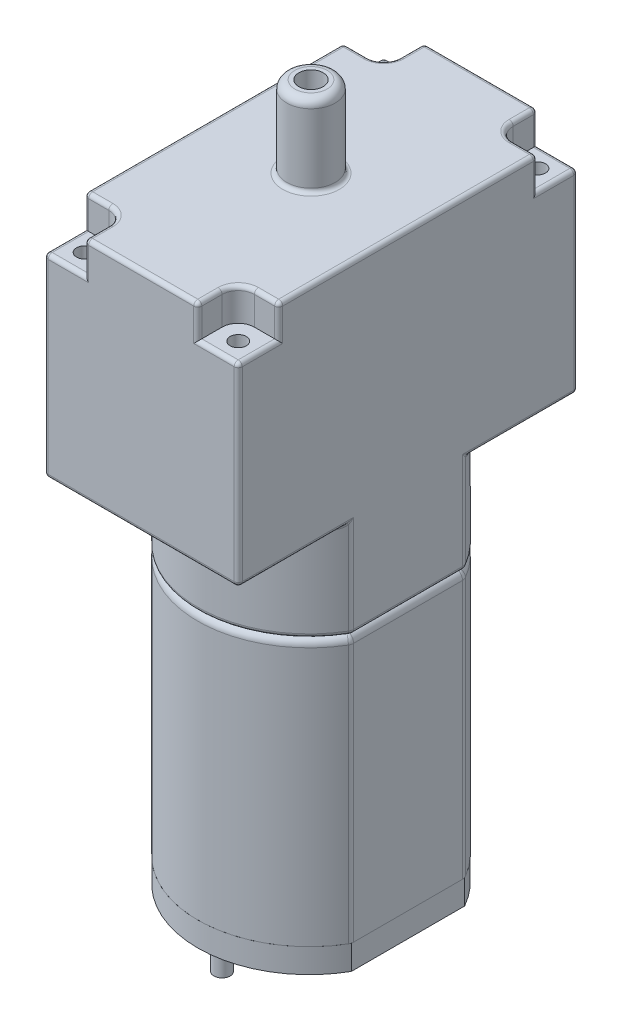
SolidWorks part; units mm, degrees
note: The reader was unsure of these and kept them because the rebuilt part matched: shared geometry of "Sketch4<3>".
ref_plane "Front Plane" through (0, 0, 0) normal (0, 0, 1) x (1, 0, 0)
ref_plane "Top Plane" through (0, 0, 0) normal (0, 1, 0) x (1, 0, 0)
ref_plane "Right Plane" through (0, 0, 0) normal (1, 0, 0) x (0, 0, -1)
sketch "Sketch1" plane through (0, 0, 0) normal (0, 1, 0) x (1, 0, 0)
  line L0 (-6, 3.5) -> (-6, -3.5)
  line L3 (-16.5353, 7) -> (21.0822, 7) construction
  line L4 (-19.3341, -7) -> (20.6889, -7) construction
  line L5 (6, 3.5) -> (6, -3.5)
  arc A1 (-6, 3.5) -> (6, 3.5) centre (0, 0.1071) cw
  arc A2 (-6, -3.5) -> (6, -3.5) centre (0, -0.1071) ccw
  point P3 (6, 0)
  dimension "D2" = 14
  dimension "D1" = 12
  dimension "D3" = 6
  dimension "D4" = 7
  dimension "D5" = 7
extrude "Boss-Extrude1" add sketch "Sketch1" along normal blind 1.5 contours A1 L5 A2 L0
sketch "Sketch3" plane through (0, 0, 0) normal (0, -1, 0) x (1, 0, 0)
  circle A0 centre (0, 0) radius 3
  dimension "D1" = 6
extrude "Boss-Extrude3" add sketch "Sketch3" along normal blind 1
sketch "Sketch4" plane through (0, 0, 0) normal (0, -1, 0) x (1, 0, 0)
  circle A0 centre (0, -5.5) radius 0.5
  circle A1 centre (0, 5.5) radius 0.5
  dimension "D3" = 1
  dimension "D1" = 11
  dimension "D2" = 5.5
extrude "Boss-Extrude5" add sketch "Sketch4" along normal blind 2 contours A1
extrude "Boss-Extrude6" add sketch "Sketch4<3>" along normal blind 2 contours A0
sketch "Sketch4<3>" plane through (0, 0, 0) normal (0, -1, 0) x (1, 0, 0) same geometry as "Sketch4"
sketch "Sketch2" plane through (0, 1.5, 0) normal (0, 1, 0) x (1, 0, 0)
  line L2 (-6, 3.5) -> (-6, -3.5)
  line L3 (6, -3.5) -> (6, 3.5)
  line L4 (-6, 3.5) -> (-6, -3.5)
  line L5 (6, -3.5) -> (6, 3.5)
  arc A2 (-6, -3.5) -> (6, -3.5) centre (0, -0.1071) ccw
  arc A3 (6, 3.5) -> (-6, 3.5) centre (0, 0.1071) ccw
  arc A4 (-6, -3.5) -> (6, -3.5) centre (0, -0.1071) ccw
  arc A5 (6, 3.5) -> (-6, 3.5) centre (0, 0.1071) ccw
  dimension "D1" = 0
extrude "Boss-Extrude2" add sketch "Sketch2" along normal blind 16.5 separate body
sketch "Sketch5" plane through (0, 18, 0) normal (0, 1, 0) x (1, 0, 0)
  line L2 (-6, 3.5) -> (-6, -3.5)
  line L3 (6, -3.5) -> (6, 3.5)
  line L4 (-6, 3.5) -> (-6, -3.5)
  line L5 (6, -3.5) -> (6, 3.5)
  arc A2 (6, 3.5) -> (-6, 3.5) centre (0, 0.1071) ccw
  arc A3 (-6, -3.5) -> (6, -3.5) centre (0, -0.1071) ccw
  arc A4 (6, 3.5) -> (-6, 3.5) centre (0, 0.1071) ccw
  arc A5 (-6, -3.5) -> (6, -3.5) centre (0, -0.1071) ccw
  dimension "D1" = 0
extrude "Boss-Extrude7" add sketch "Sketch5" along normal blind 6 separate body
sketch "Sketch6" plane through (0, 24, 0) normal (0, 1, 0) x (1, 0, 0)
  line L0 (6, -3.5) -> (6, 3.5) construction
  line L1 (-6, 10.5) -> (6, 10.5)
  line L2 (-6, 10.5) -> (-6, -10.5)
  line L3 (-6, -10.5) -> (6, -10.5)
  line L4 (6, 10.5) -> (6, -10.5)
  line L5 (-6, 10.5) -> (6, -10.5) construction
  line L6 (-6, -10.5) -> (6, 10.5) construction
  point P0 (0, 0)
  dimension "D1" = 21
extrude "Boss-Extrude8" add sketch "Sketch6" along normal blind 14
sketch "Sketch7" plane through (0, 38, 0) normal (0, 1, 0) x (1, 0, 0)
  circle A0 centre (0, 0) radius 1.5
  circle A1 centre (0, 0) radius 0.75
  dimension "D1" = 3
  dimension "D2" = 1.5
extrude "Boss-Extrude9" add sketch "Sketch7" along normal blind 5
sketch "Sketch8" plane through (0, 38, 0) normal (0, 1, 0) x (1, 0, 0)
  line L1 (-6, 10.5) -> (-3.5, 10.5)
  line L2 (-6, 10.5) -> (-6, 8)
  line L3 (-6, 8) -> (-4.5, 8)
  line L4 (-3.5, 10.5) -> (-3.5, 9)
  arc A0 (-3.5, 9) -> (-4.5, 8) centre (-4.5, 9) cw
  dimension "D2" = 1
  dimension "D1" = 2.5
extrude "Cut-Extrude1" cut sketch "Sketch8" against normal blind 2
mirror "Mirror1" about plane through (0, 0, 0) normal (1, 0, 0) of "Cut-Extrude1" second plane through (0, 0, 0) second plane normal (0, 0, 1)
hole_wizard "Ø1.0mm Dowel Hole1" positions "Sketch9" profile "Sketch10" hole size "Ø1.0" standard "ISO" end condition through all
sketch "Sketch9" plane through (0, 36, 0) normal (0, 1, 0) x (1, 0, 0)
  line L0 (-3.5, 10.5) -> (-6, 10.5) construction
  line L1 (-6, 10.5) -> (-6, 8) construction
  line L2 (6, -10.5) -> (6, -8) construction
  line L3 (3.5, -10.5) -> (6, -10.5) construction
  point P0 (-4.75, 9.25)
  point P2 (4.75, 9.25)
  point P4 (4.75, -9.25)
  point P6 (-4.75, -9.25)
  point P16 (-4.75, 10.5)
  point P19 (-6, 9.25)
  point P22 (6, -9.25)
  point P25 (4.75, -10.5)
sketch "Sketch10" plane through (-4.75, 36, -9.25) normal (1, 0, 0) x (0, 0, 1)
  line L0 (0, 0) -> (0, 38)
  line L1 (0, 38) -> (0.5, 38)
  line L2 (0.5, 38) -> (0.5, 0)
  line L5 (0.5, 0) -> (0, 0)
  line L11 (0, -6.35) -> (0, 107.95) construction
  dimension "Thru Hole Dia." = 1
  dimension "Thru Hole Depth" = 38
fillet "Fillet1" radius 0.5 4 edges at (6, 9.75, -3.5) (6, 9.75, 3.5) (-6, 9.75, -3.5) (-6, 9.75, 3.5)
fillet "Fillet2" radius 0.5 8 edges at (0, 18, 7) (-5.9822, 18, 3.4979) (-6, 18, 0) (-5.9822, 18, -3.4979) (0, 18, -7) (5.9822, 18, -3.4979) (6, 18, 0) (5.9822, 18, 3.4979)
fillet "Fillet3" radius 0.5 4 edges at (-6, 21, 3.5) (-6, 21, -3.5) (6, 21, -3.5) (6, 21, 3.5)
fillet "Fillet4" radius 0.25 8 edges at (-5.9822, 18, 3.4979) (-6, 18, 0) (-5.9822, 18, -3.4979) (0, 18, -7) (5.9822, 18, -3.4979) (6, 18, 0) (5.9822, 18, 3.4979) (0, 18, 7)
fillet "Fillet5" radius 0.25 47 edges at (-5.9822, 24, 3.4979) (-5.9822, 24, -3.4979) (5.9822, 24, -3.4979) (5.9822, 24, 3.4979) (6, 24, 6.9329) (6, 24, -6.9329) (0, 24, -10.5) (-6, 24, -6.9329) (-6, 24, 6.9329) (0, 24, 10.5) (0, 38, 1.5) (-6, 38, 0) (-6, 30, -10.5) (-6, 36, -9.25) (-6, 37, -8) (-4.75, 36, -10.5) (-3.5, 37, -10.5) (-5.25, 38, -8) (-3.7929, 38, -8.2929) (-3.5, 38, -9.75) (0, 38, 10.5) (-6, 30, 10.5) (-5.25, 38, 8) (-6, 37, 8) (-3.7929, 38, 8.2929) (-3.5, 38, 9.75) (-3.5, 37, 10.5) (-6, 36, 9.25) (-4.75, 36, 10.5) (0, 38, -10.5) (6, 30, -10.5) (5.25, 38, -8) (6, 37, -8) (3.7929, 38, -8.2929) (3.5, 38, -9.75) (3.5, 37, -10.5) (6, 36, -9.25) (4.75, 36, -10.5) (6, 30, 10.5) (6, 38, 0) (6, 36, 9.25) (6, 37, 8) (4.75, 36, 10.5) (3.5, 37, 10.5) (5.25, 38, 8) (3.7929, 38, 8.2929) (3.5, 38, 9.75)
fillet "Fillet6" radius 0.5 1 edges at (0, 43, 1.5)
fillet "Fillet7" radius 0.25 10 edges at (5.9916, 24.1857, -3.4571) (5.8841, 24.039, -3.6973) (-5.9916, 24.1857, -3.4571) (-5.8302, 24.0132, -3.7841) (-5.9916, 24.1857, 3.4571) (-5.8841, 24.039, 3.6973) (5.9916, 24.1857, 3.4571) (5.8302, 24.0132, 3.7841) (0, 24, -7) (0, 24, 7)
equation "\"D3@Sketch1\"=\"D1@Sketch1\"/2"
equation "\"D5@Sketch1\"=\"D2@Sketch1\"/2"
equation "\"D2@Sketch4\"=\"D1@Sketch4\"/2"
